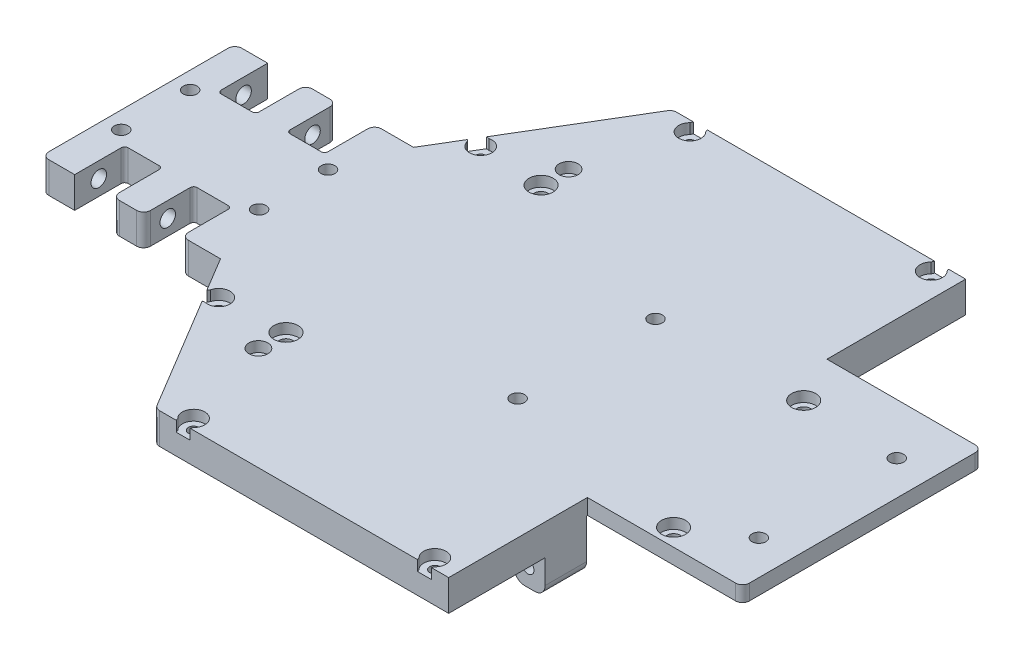
SolidWorks part; units mm, degrees
ref_plane "Front Plane" through (0, 0, 0) normal (0, 0, 1) x (1, 0, 0)
ref_plane "Top Plane" through (0, 0, 0) normal (0, 1, 0) x (1, 0, 0)
ref_plane "Right Plane" through (0, 0, 0) normal (1, 0, 0) x (0, 0, -1)
sketch "Sketch1" plane through (0, 0, 0) normal (0, 1, 0) x (1, 0, 0)
  line L0 (-78.0026, 25) -> (-28.0026, 25)
  line L1 (1.9974, 75) -> (86.9974, 75)
  line L2 (-78.0026, 25) -> (-78.0026, -25)
  line L3 (1.9974, -75) -> (86.9974, -75)
  line L4 (86.9974, 75) -> (86.9974, -75)
  line L7 (-28.0026, 25) -> (1.9974, 75)
  line L8 (1.9974, -75) -> (-28.0026, -25)
  line L9 (-28.0026, -25) -> (-78.0026, -25)
  point P0 (0, 0)
  dimension "D1" = 30
  dimension "D2" = 30
  dimension "D3" = 50
  dimension "D4" = 50
  dimension "D5" = 50
  dimension "D6" = 165
  dimension "D7" = 75
  dimension "D8" = 50
  dimension "D9" = 50
  dimension "D10" = 150
extrude "Boss-Extrude1" add sketch "Sketch1" along normal blind 9
sketch "Sketch3" plane through (0, 9, 0) normal (0, 1, 0) x (1, 0, 0)
  line L1 (-28.0026, 25) -> (-78.0026, 25) construction
  line L4 (-78.0026, 25) -> (-78.0026, -25) construction
  circle A0 centre (-73.0026, 10) radius 2
  circle A1 centre (-33.0026, 10) radius 2
  circle A2 centre (-33.0026, -10) radius 2
  circle A3 centre (-73.0026, -10) radius 2
  dimension "D5" = 4
  dimension "D6" = 4
  dimension "D7" = 4
  dimension "D8" = 4
  dimension "D1" = 40
  dimension "D2" = 20
  dimension "D3" = 20
  dimension "D4" = 40
  dimension "D9" = 15
  dimension "D10" = 5
  dimension "D11" = 15
  dimension "D12" = 5
extrude "Cut-Extrude1" cut sketch "Sketch3" against normal through all
sketch "Sketch4" plane through (86.9974, 0, 0) normal (1, 0, 0) x (0, 0, -1)
  line L0 (-75, 9) -> (75, 9) construction
  line L1 (-34.75, 9) -> (34.75, 9)
  line L2 (-34.75, 9) -> (-34.75, 4.5)
  line L3 (-34.75, 4.5) -> (34.75, 4.5)
  line L4 (34.75, 9) -> (34.75, 4.5)
  line L5 (-75, 9) -> (-75, 0) construction
  line L6 (75, 9) -> (75, 0) construction
  dimension "D1" = 4.5
  dimension "D2" = 40.25
  dimension "D3" = 40.25
extrude "Boss-Extrude2" add sketch "Sketch4" along normal blind 45
sketch "Sketch5" plane through (86.9974, 0, 0) normal (1, 0, 0) x (0, 0, -1)
  line L1 (-35, 4.5) -> (35, 4.5)
  line L2 (-35, 4.5) -> (-35, 0)
  line L3 (-35, 0) -> (35, 0)
  line L4 (35, 4.5) -> (35, 0)
  line L5 (34.75, 4.5) -> (34.75, 9) construction
  dimension "D1" = 70
  dimension "D2" = 0.25
extrude "Cut-Extrude2" cut sketch "Sketch5" against normal blind 50
sketch "Sketch6" plane through (0, 9, 0) normal (0, 1, 0) x (1, 0, 0)
  line L2 (131.9974, 34.75) -> (131.9974, -34.75) construction
  circle A0 centre (51.9974, 20) radius 2
  circle A1 centre (51.9974, -20) radius 2
  circle A2 centre (121.9974, 20) radius 2
  circle A3 centre (121.9974, -20) radius 2
  dimension "D1" = 4
  dimension "D2" = 4
  dimension "D3" = 4
  dimension "D4" = 4
  dimension "D8" = 70
  dimension "D9" = 0
  dimension "D11" = 10
  dimension "D5" = 10
  dimension "D10" = 40
  dimension "D6" = 20
  dimension "D7" = 40
  dimension "D12" = 20
  dimension "D13" = 70
extrude "Cut-Extrude4" cut sketch "Sketch6" against normal blind 50
fillet "Fillet1" radius 2 4 edges at (-28.0026, 4.5, -25) (1.9974, 4.5, -75) (1.9974, 4.5, 75) (-28.0026, 4.5, 25)
fillet "Fillet2" radius 2 2 edges at (131.9974, 6.75, -34.75) (131.9974, 6.75, 34.75)
sketch "Sketch7" plane through (0, 9, 0) normal (0, 1, 0) x (1, 0, 0)
  line L0 (-78.0026, -25) -> (-29.1349, -25) construction
  line L1 (-68.5026, -25) -> (-57.5026, -25)
  line L2 (-68.5026, -25) -> (-68.5026, -13.5)
  line L3 (-68.5026, -13.5) -> (-57.5026, -13.5)
  line L4 (-57.5026, -25) -> (-57.5026, -13.5)
  line L5 (-78.0026, 25) -> (-78.0026, -25) construction
  line L6 (-48.5026, -25) -> (-37.5026, -25)
  line L7 (-48.5026, -25) -> (-48.5026, -13.5)
  line L8 (-48.5026, -13.5) -> (-37.5026, -13.5)
  line L9 (-37.5026, -25) -> (-37.5026, -13.5)
  dimension "D1" = 9.5
  dimension "D2" = 11
  dimension "D3" = 9
  dimension "D4" = 11
  dimension "D5" = 11.5
  dimension "D6" = 11.5
extrude "Cut-Extrude5" cut sketch "Sketch7" against normal through all
sketch "Sketch8" plane through (-78.0026, 0, 0) normal (-1, 0, 0) x (0, 0, 1)
  line L0 (-25, 9) -> (25, 9) construction
  line L1 (25, 9) -> (25, 0) construction
  circle A0 centre (21, 4.5) radius 2.25
  dimension "D2" = 4.5
  dimension "D1" = 4.5
  dimension "D3" = 4
extrude "Cut-Extrude6" cut sketch "Sketch8" against normal blind 50
sketch "Sketch10" plane through (-78.0026, 0, 0) normal (-1, 0, 0) x (0, 0, 1)
  circle A0 centre (21, 4.5) radius 3.5
  dimension "D1" = 7
extrude "Cut-Extrude8" cut sketch "Sketch10" against normal blind 4
sketch "Sketch11" plane through (-37.5026, 0, 0) normal (-1, 0, 0) x (0, 0, 1)
  line L24 (16.9585, 4.5) -> (16.9585, -3.0678)
  line L25 (25.0415, 4.5) -> (23.0207, 8)
  line L26 (23.0207, 8) -> (18.9793, 8)
  line L27 (18.9793, 8) -> (16.9585, 4.5)
  line L31 (16.9585, -3.0678) -> (25.0415, -3.0678)
  line L32 (25.0415, -3.0678) -> (25.0415, 4.5)
  line L34 (18.39, 1) -> (22.4314, 1) [skipped]
  line L35 (16.6639, 5.0103) -> (17.6743, 3.2603) [skipped]
  line L36 (25.3361, 5.0103) -> (26.3465, 6.7603) [skipped]
  arc A1 (24.0311, 6.25) -> (17.9689, 6.25) centre (21, 4.5) ccw construction
extrude "Cut-Extrude9" cut sketch "Sketch11" against normal blind 5 from offset 3 offset against normal yes
mirror "Mirror8" about plane through (0, 0, 0) normal (0, 0, 1) of "Cut-Extrude9", "Cut-Extrude8", "Cut-Extrude6", "Cut-Extrude5"
fillet "Fillet6" radius 1 8 edges at (-57.5026, 4.5, 13.5) (-48.5026, 4.5, 13.5) (-37.5026, 4.5, 13.5) (-68.5026, 4.5, 13.5) (-68.5026, 4.5, -13.5) (-57.5026, 4.5, -13.5) (-48.5026, 4.5, -13.5) (-37.5026, 4.5, -13.5)
sketch "Sketch12" plane through (0, 0, 0) normal (0, -1, 0) x (1, 0, 0)
  line L3 (-27.42, 25.971) -> (1.4148, 74.029) construction
  line L4 (3.1298, 75) -> (86.9974, 75) construction
  line L6 (86.9974, 75) -> (86.9974, 35) construction
  line L7 (55, 0) -> (-55, 0) construction
  circle A0 centre (9.9974, 72) radius 1.5
  circle A1 centre (79.9974, 72) radius 1.5
  circle A2 centre (-16.704, 38) radius 1.5
  circle A3 centre (-16.704, -38) radius 1.5
  circle A4 centre (79.9974, -72) radius 1.5
  circle A5 centre (9.9974, -72) radius 1.5
  dimension "D1" = 3
  dimension "D2" = 3
  dimension "D4" = 3
  dimension "D6" = 3
  dimension "D3" = 3
  dimension "D5" = 3
  dimension "D7" = 7
  dimension "D8" = 70
  dimension "D9" = 37
extrude "Cut-Extrude10" cut sketch "Sketch12" against normal blind 10
sketch "Sketch13" plane through (0, 9, 0) normal (0, 1, 0) x (1, 0, 0)
  line L0 (-55, 0) -> (55, 0) construction
  circle A0 centre (-16.704, 38) radius 3.25
  circle A1 centre (9.9974, 72) radius 3.25
  circle A2 centre (79.9974, 72) radius 3.25
  circle A3 centre (79.9974, -72) radius 3.25
  circle A4 centre (9.9974, -72) radius 3.25
  circle A5 centre (-16.704, -38) radius 3.25
  dimension "D1" = 6.5
  dimension "D2" = 6.5
  dimension "D3" = 6.5
extrude "Cut-Extrude11" cut sketch "Sketch13" against normal blind 3
chamfer "Chamfer1" distance 1 angle 45 12 edges at (81.2474, 7.5, 75) (78.7474, 7.5, 75) (11.2474, 7.5, 75) (8.7474, 7.5, 75) (-18.6333, 7.5, 40.6154) (-19.9196, 7.5, 38.4716) (81.2474, 7.5, -75) (78.7474, 7.5, -75) (11.2474, 7.5, -75) (8.7474, 7.5, -75) (-19.9196, 7.5, -38.4716) (-18.6333, 7.5, -40.6154) first distance on face at (79.9974, 7.5, 71.875) first distance on face at (9.9974, 7.5, 71.875) first distance on face at (-16.5968, 7.5, 37.9357) first distance on face at (79.9974, 7.5, -71.875) first distance on face at (9.9974, 7.5, -71.875) first distance on face at (-16.5968, 7.5, -37.9357)
sketch "Sketch14" plane through (0, 0, 25) normal (0, 0, 1) x (1, 0, 0)
  line L1 (-37.5026, 9) -> (-25.5026, 9)
  line L2 (-37.5026, 9) -> (-37.5026, 0)
  line L3 (-37.5026, 0) -> (-25.5026, 0)
  line L4 (-25.5026, 9) -> (-25.5026, 0)
  dimension "D1" = 12
extrude "Boss-Extrude3" add sketch "Sketch14" along normal blind 3
mirror "Mirror10" about plane through (0, 0, 0) normal (0, 0, 1) of "Boss-Extrude3"
sketch "Sketch15" plane through (0, 4.5, 0) normal (0, -1, 0) x (1, 0, 0)
  line L0 (131.9974, 32.75) -> (131.9974, -32.75) construction
  line L1 (129.9974, 34.75) -> (86.9974, 34.75) construction
  line L2 (86.9974, -75) -> (3.1298, -75) construction
  line L3 (86.9974, -35) -> (86.9974, -75) construction
  circle A0 centre (93.9974, -21) radius 2
  circle A1 centre (106.9974, 29.75) radius 2
  dimension "D3" = 4
  dimension "D5" = 4
  dimension "D1" = 54
  dimension "D2" = 7
  dimension "D4" = 25
  dimension "D6" = 5
extrude "Cut-Extrude12" cut sketch "Sketch15" against normal through all
sketch "Sketch16" plane through (0, 0, 0) normal (0, -1, 0) x (1, 0, 0)
  line L1 (86.9974, -75) -> (3.1298, -75) construction
  line L2 (55, 0) -> (-55, 0) construction
  circle A0 centre (1.7974, -37) radius 2
  circle A2 centre (1.7974, -45) radius 1.5
  circle A3 centre (1.7974, 45) radius 1.5
  circle A4 centre (1.7974, 37) radius 2
  dimension "D1" = 4
  dimension "D2" = 0
  dimension "D8" = 3
  dimension "D4" = 38
  dimension "D5" = 28
  dimension "D7" = 8
extrude "Cut-Extrude13" cut sketch "Sketch16" against normal blind 10
sketch "Sketch17" plane through (0, 0, 0) normal (0, -1, 0) x (1, 0, 0)
  line L0 (3.1298, 75) -> (86.9974, 75) construction
  line L1 (27.9974, 47) -> (36.9974, 47)
  line L2 (27.9974, 47) -> (27.9974, 35)
  line L3 (27.9974, 35) -> (36.9974, 35)
  line L4 (36.9974, 47) -> (36.9974, 35)
  line L5 (77.9974, 47) -> (86.9974, 47)
  line L6 (77.9974, 47) -> (77.9974, 35)
  line L7 (77.9974, 35) -> (86.9974, 35)
  line L8 (86.9974, 47) -> (86.9974, 35)
  line L9 (86.9974, 75) -> (86.9974, 35) construction
  dimension "D1" = 9
  dimension "D2" = 9
  dimension "D3" = 41
  dimension "D4" = 12
  dimension "D5" = 12
  dimension "D6" = 28
  dimension "D7" = 0
  dimension "D8" = 28
extrude "Boss-Extrude4" add sketch "Sketch17" along normal blind 10
sketch "Sketch18" plane through (0, 0, 47) normal (0, 0, 1) x (1, 0, 0)
  line L0 (27.9974, -10) -> (27.9974, 0) construction
  line L1 (77.9974, -10) -> (77.9974, 0) construction
  circle A0 centre (32.9974, -4.8167) radius 1.75
  circle A1 centre (81.9974, -4.8167) radius 1.75
  dimension "D2" = 3.5
  dimension "D4" = 3.5
  dimension "D1" = 5
  dimension "D3" = 4
extrude "Cut-Extrude14" cut sketch "Sketch18" against normal through all
fillet "Fillet8" radius 3 6 edges at (27.9974, 0, 41) (32.4974, 0, 35) (36.9974, -10, 41) (27.9974, -10, 41) (77.9974, -10, 41) (86.9974, -10, 41)
chamfer "Chamfer2" distance 0.5 angle 45 14 edges at (79.9974, 0, 70.5) (79.9974, 0, -70.5) (9.9974, 0, -70.5) (1.7974, 0, -46.5) (1.7974, 0, -39) (-73.0026, 0, -8) (-73.0026, 0, 12) (-33.0026, 0, 12) (-33.0026, 0, -8) (-16.704, 0, -36.5) (-16.704, 0, 36.5) (1.7974, 0, 46.5) (9.9974, 0, 70.5) (1.7974, 0, 39)
sketch "Sketch19" plane through (0, 9, 0) normal (0, 1, 0) x (1, 0, 0)
  circle A0 centre (1.7974, 45) radius 2.75
  circle A1 centre (1.7974, -45) radius 2.75
  circle A2 centre (1.7974, -37) radius 3.5
  circle A3 centre (106.9974, -29.75) radius 3.5
  circle A4 centre (1.7974, 37) radius 3.5
  circle A5 centre (93.9974, 21) radius 3.5
  dimension "D1" = 7
  dimension "D2" = 5.5
  dimension "D3" = 5.5
  dimension "D4" = 7
  dimension "D5" = 7
  dimension "D6" = 7
extrude "Cut-Extrude15" cut sketch "Sketch19" against normal blind 3
sketch "Sketch20" plane through (0, 0, -25) normal (0, 0, -1) x (-1, 0, 0)
  line L1 (57.5026, 0) -> (48.5026, 0)
  line L2 (57.5026, 0) -> (57.5026, 9)
  line L3 (57.5026, 9) -> (48.5026, 9)
  line L4 (48.5026, 0) -> (48.5026, 9)
  line L5 (68.5026, 9) -> (78.0026, 9)
  line L6 (68.5026, 9) -> (68.5026, 0)
  line L7 (68.5026, 0) -> (78.0026, 0)
  line L8 (78.0026, 9) -> (78.0026, 0)
extrude "Boss-Extrude5" add sketch "Sketch20" along normal blind 3
mirror "Mirror11" about plane through (0, 0, 0) normal (0, 0, 1) of "Boss-Extrude5"
fillet "Fillet9" radius 2 8 edges at (-37.5026, 4.5, 28) (-48.5026, 4.5, 28) (-57.5026, 4.5, 28) (-48.5026, 4.5, -28) (-57.5026, 4.5, -28) (-37.5026, 4.5, -28) (-78.0026, 4.5, 28) (-78.0026, 4.5, -28)
equation "\"D2@Sketch6\"=\"D4@Sketch6\""
equation "\"D5@Sketch7\"=\"D6@Sketch7\""
equation "\"D3@Sketch4\"=\"D2@Sketch4\""
